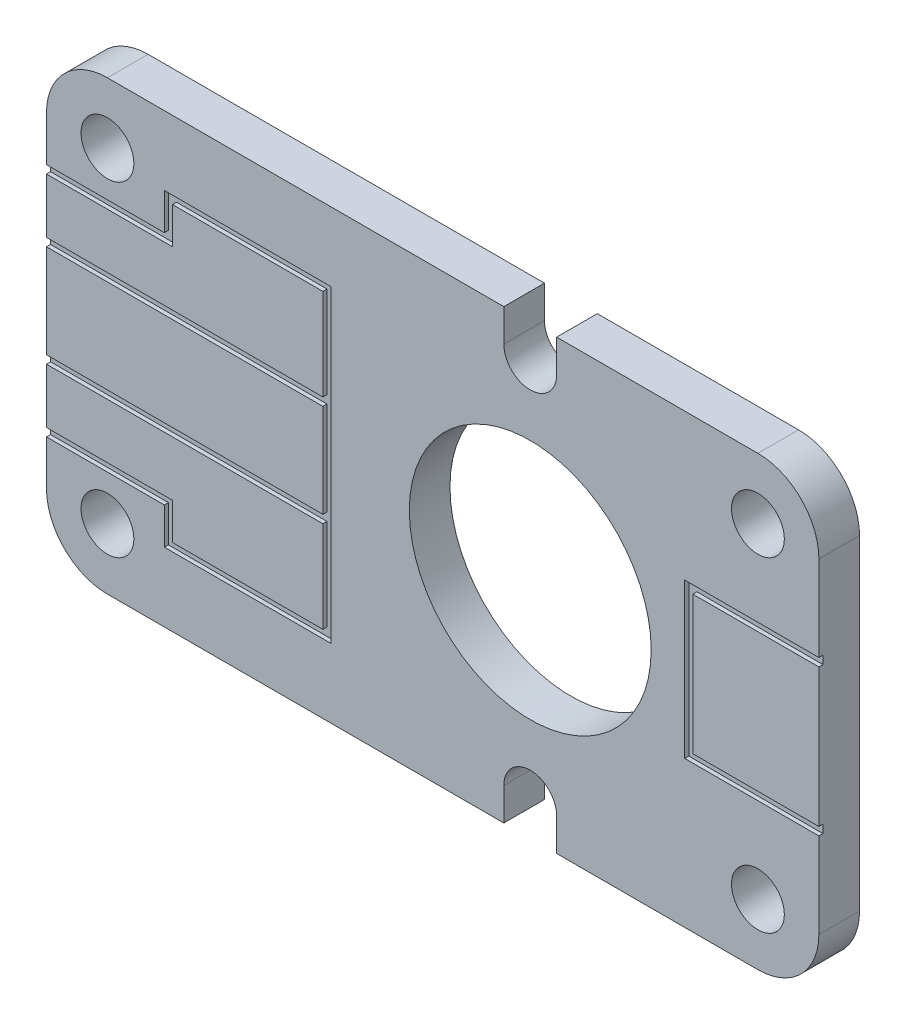
SolidWorks part; units mm, degrees
note: The reader was unsure of these and kept them because the rebuilt part matched: shared geometry of "Model<3>".
ref_plane "Спереди" through (0, 0, 0) normal (0, 0, 1) x (1, 0, 0)
ref_plane "Сверху" through (0, 0, 0) normal (0, 1, 0) x (1, 0, 0)
ref_plane "Справа" through (0, 0, 0) normal (1, 0, 0) x (0, 0, -1)
sketch "Model" plane through (0, 0, 0) normal (0, 0, 1) x (1, 0, 0)
  line L0 (-11.9, -2.9) -> (-9, -2.9)
  line L1 (-10.4, -5.5) -> (-4.7, -5.5)
  line L2 (-5.1, -1.15) -> (-11.9, -1.15)
  line L3 (7.1, 1.6) -> (7.1, 4)
  line L4 (-5.1, 1.15) -> (-5.1, -1.15)
  line L5 (-5.1, 1.15) -> (-11.9, 1.15)
  line L6 (0.65, -5.5) -> (3.6, -5.5)
  line L7 (-11.9, -2.6) -> (-11.9, -4)
  line L8 (-0.65, 4.7) -> (-0.65, 5.5)
  line L9 (-11.9, -1.35) -> (-5.1, -1.35)
  line L11 (0.65, -4.7) -> (0.65, -5.5)
  line L12 (0.65, 5.5) -> (3.6, 5.5)
  line L13 (-11.9, 1.5) -> (-11.9, 1)
  line L14 (-9, -2.9) -> (-9, -3.8)
  line L15 (-9, -3.8) -> (-4.9, -3.8)
  line L16 (-4.7, 5.5) -> (-0.65, 5.5)
  line L17 (-4.7, -5.5) -> (-0.65, -5.5)
  line L18 (-0.65, -4.7) -> (-0.65, -5.5)
  line L19 (-4.9, -1.45) -> (-4.9, -3.8)
  line L20 (-11.9, -1.5) -> (-11.9, -2.6)
  line L21 (7.1, -4) -> (7.1, -1.6)
  line L22 (-4.9, 1.25) -> (-4.9, -1.45)
  line L23 (5.6, 5.5) -> (3.6, 5.5)
  line L24 (7.1, 1.6) -> (7.1, -1.6)
  line L26 (-11.9, 2.6) -> (-11.9, 1.5)
  line L27 (-4.9, 1.25) -> (-4.9, 3.8)
  line L28 (-11.9, 4) -> (-11.9, 2.6)
  line L30 (-9, 3.8) -> (-4.9, 3.8)
  line L31 (3.6, -5.5) -> (5.6, -5.5)
  line L32 (-9, 2.9) -> (-9, 3.8)
  line L33 (-4.7, 5.5) -> (-10.4, 5.5)
  line L34 (0.65, 4.7) -> (0.65, 5.5)
  line L35 (-11.9, -1) -> (-11.9, -1.5)
  line L36 (-11.9, 1) -> (-11.9, -1)
  line L37 (-5.1, -1.35) -> (-5.1, -3.6)
  line L38 (7.1, 1.9) -> (3.8, 1.9)
  line L39 (3.8, 1.9) -> (3.8, -1.9)
  line L40 (7.1, -1.9) -> (3.8, -1.9)
  line L41 (7.1, 1.7) -> (4, 1.7)
  line L42 (4, 1.7) -> (4, -1.7)
  line L43 (7.1, -1.7) -> (4, -1.7)
  line L50 (-11.9, 1.35) -> (-5.1, 1.35)
  line L51 (-5.1, 1.35) -> (-5.1, 3.6)
  line L52 (-8.8, 3.6) -> (-5.1, 3.6)
  line L53 (-8.8, 2.7) -> (-8.8, 3.6)
  line L54 (-8.8, 2.7) -> (-11.9, 2.7)
  line L55 (-8.8, -3.6) -> (-5.1, -3.6)
  line L56 (-8.8, -2.7) -> (-8.8, -3.6)
  line L57 (-11.9, -2.7) -> (-8.8, -2.7)
  line L58 (-9, 2.9) -> (-11.9, 2.9)
  arc A0 (-0.65, 4.7) -> (0.65, 4.7) centre (0, 4.7) ccw
  circle A1 centre (5.6, -4) radius 0.65
  circle A2 centre (0, 0) radius 2.9746
  arc A3 (7.1, 4) -> (5.6, 5.5) centre (5.6, 4) ccw
  arc A4 (0.65, -4.7) -> (-0.65, -4.7) centre (0, -4.7) ccw
  circle A5 centre (5.6, 4) radius 0.65
  arc A6 (5.6, -5.5) -> (7.1, -4) centre (5.6, -4) ccw
  circle A7 centre (-10.4, -4) radius 0.65
  arc A8 (-11.9, -4) -> (-10.4, -5.5) centre (-10.4, -4) ccw
  arc A9 (-10.4, 5.5) -> (-11.9, 4) centre (-10.4, 4) ccw
  circle A10 centre (-10.4, 4) radius 0.65
extrude "Бобышка-Вытянуть1" add sketch "Model" against normal blind 1
extrude "Вырез-Вытянуть1" cut sketch "Model<3>" against normal blind 0.1
sketch "Model<3>" plane through (0, 0, 0) normal (0, 0, 1) x (1, 0, 0) same geometry as "Model"
